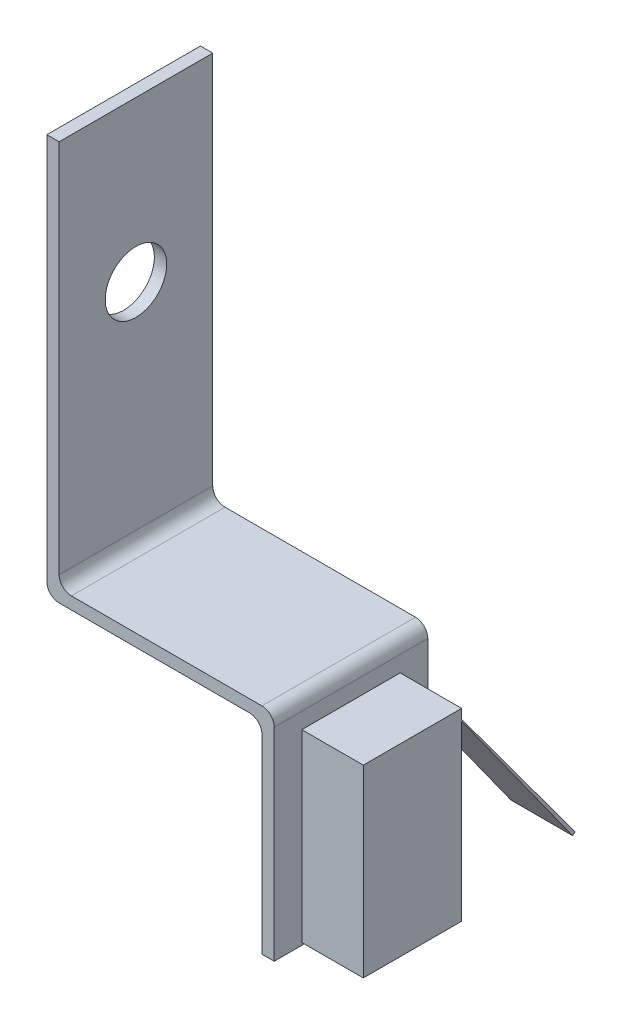
SolidWorks part; units mm, degrees
ref_plane "Alzado" through (0, 0, 0) normal (0, 0, 1) x (1, 0, 0)
ref_plane "Planta" through (0, 0, 0) normal (0, 1, 0) x (1, 0, 0)
ref_plane "Vista lateral" through (0, 0, 0) normal (1, 0, 0) x (0, 0, -1)
sketch "Sketch1" plane through (0, 0, 0) normal (0, 0, 1) x (1, 0, 0)
  line L0 (0, 0) -> (2, 0)
  line L1 (55, 0) -> (-55, 0) construction
  line L2 (2, 0) -> (2, -63)
  line L3 (2, -63) -> (37, -63)
  line L4 (37, -63) -> (37, -98)
  line L5 (37, -98) -> (35, -98)
  line L6 (35, -98) -> (35, -65)
  line L7 (35, -65) -> (0, -65)
  line L8 (0, -55) -> (0, 55) construction
  line L9 (0, -65) -> (0, 0)
  dimension "D1" = 2
  dimension "D2" = 63
  dimension "D3" = 2
  dimension "D4" = 35
  dimension "D5" = 35
  dimension "D6" = 2
extrude "Boss-Extrude1" add sketch "Sketch1" along normal blind 12.5 and the other way blind 12.5
hole_wizard "Ø10.0mm Dowel Hole1" positions "3DSketch1" profile "Sketch2" hole size "Ø10.0" standard "ISO" end condition through all
sketch3d "3DSketch1"
  point P0 (2, -26, 0)
  dimension "D1" = 0
  dimension "D2" = 26
sketch "Sketch2" plane through (2, -26, 0) normal (0, 1, 0) x (0, 0, -1)
  line L0 (0, 0) -> (0, 2)
  line L1 (0, 2) -> (5, 2)
  line L2 (5, 2) -> (5, 0)
  line L5 (5, 0) -> (0, 0)
  line L11 (0, -6.35) -> (0, 107.95) construction
  dimension "Thru Hole Dia." = 10
  dimension "Thru Hole Depth" = 2
fillet "Fillet1" radius 2 4 edges at (35, -65, 0) (0, -65, 0) (2, -63, 0) (37, -63, 0)
sketch "Sketch3" plane through (37, 0, 0) normal (1, 0, 0) x (0, 0, -1)
  line L0 (0, 20.35) -> (0, -20.35) construction
  line L1 (-8, -67.6044) -> (8, -67.6044)
  line L2 (-8, -67.6044) -> (-8, -97.6044)
  line L3 (-8, -97.6044) -> (8, -97.6044)
  line L4 (8, -67.6044) -> (8, -97.6044)
  dimension "D1" = 30
  dimension "D2" = 16
  dimension "D3" = 8
extrude "Boss-Extrude2" add sketch "Sketch3" along normal blind 10 contours L1 L4 L3 L2
sketch "Sketch4" plane through (47, 0, 0) normal (1, 0, 0) x (0, 0, -1)
  line L7 (8, -69.4104) -> (8, -69.1353)
  line L8 (26.0466, -94.5593) -> (8, -69.4104)
  line L9 (26.48, -94.2426) -> (26.0466, -94.5593)
  line L10 (8, -69.1353) -> (26.48, -94.2426)
extrude "Boss-Extrude3" add sketch "Sketch4" against normal blind 10
